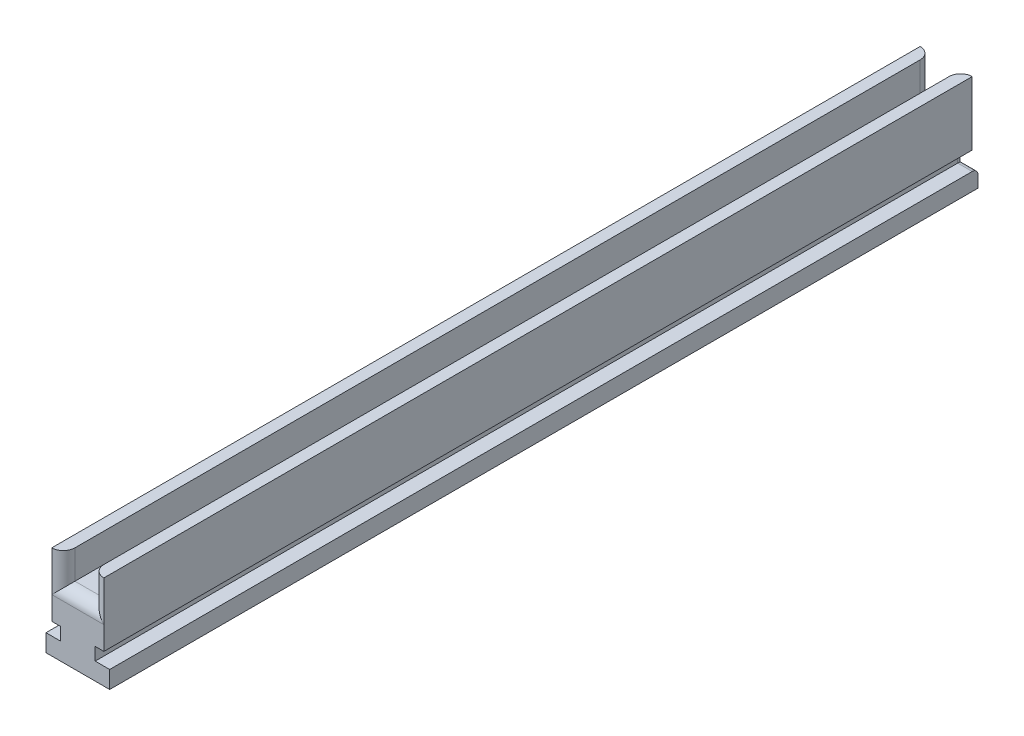
SolidWorks part; units mm, degrees
ref_plane "정면" through (0, 0, 0) normal (0, 0, 1) x (1, 0, 0)
ref_plane "윗면" through (0, 0, 0) normal (0, 1, 0) x (1, 0, 0)
ref_plane "우측면" through (0, 0, 0) normal (1, 0, 0) x (0, 0, -1)
sketch "스케치1" plane through (0, 0, 0) normal (0, 0, 1) x (1, 0, 0)
  line L0 (0, 0) -> (11.8192, 0) construction
  line L1 (0, 0) -> (0, 13.1564) construction
  line L2 (-3, 0) -> (3, 0)
  line L3 (3, 0) -> (3, -2.2)
  line L4 (3, -2.2) -> (-3, -2.2)
  line L5 (-3, -2.2) -> (-3, 0)
  line L6 (3, 0) -> (2.5, 0)
  line L7 (-5.5, -5.2) -> (5.5, -5.2)
  line L8 (-5.5, -5.2) -> (-5.5, -2.2)
  line L9 (-5.5, -2.2) -> (5.5, -2.2)
  line L10 (5.5, -5.2) -> (5.5, -2.2)
  line L11 (-5.5, -5.2) -> (5.5, -2.2) construction
  line L12 (-5.5, -2.2) -> (5.5, -5.2) construction
  line L13 (2.5, 0) -> (2.5, 11)
  line L14 (-2.5, 6) -> (2.5, 6)
  line L15 (4.5, 0) -> (4.5, 11)
  line L16 (4.5, 11) -> (2.5, 11)
  line L17 (3, 0) -> (4.5, 0)
  line L18 (-3, 0) -> (-3, -2.2)
  line L19 (-2.5, 0) -> (-2.5, 11)
  line L20 (-3, 0) -> (-2.5, 0)
  line L21 (-4.5, 11) -> (-2.5, 11)
  line L22 (-4.5, 0) -> (-4.5, 11)
  line L23 (-3, 0) -> (-4.5, 0)
  point P3 (0, -3.7)
  point P7 (0, 0)
  point P22 (0, 6)
  dimension "D1" = 6
  dimension "D2" = 2.2
  dimension "D3" = 11
  dimension "D4" = 3
  dimension "D5" = 2.5
  dimension "D6" = 6
  dimension "D7" = 2
  dimension "D8" = 5
extrude "보스-돌출1" add sketch "스케치1" along normal blind 150 contours L23 L2 L19 L21 L22 | L19 L2 L13 L14 | L2 L17 L15 L16 L13 | L5 L4 L3 L2 | L7 L10 L9 L4 L8 region at (-3.5, 5.5, 0) region at (0, -1.1, 0) region at (0, 3, 0) region at (0, -3.7, 0) region at (3.5, 5.5, 0)
fillet "필렛1" radius 2 6 edges at (-2.5, 8.5, 0) (2.5, 8.5, 0) (-2.5, 8.5, 150) (2.5, 8.5, 150) (0, 6, 0) (0, 6, 150)
fillet "필렛2" radius 1 4 edges at (-4.25, -2.2, 0) (4.25, -2.2, 0) (-3, -1.1, 0) (3, -1.1, 0)
